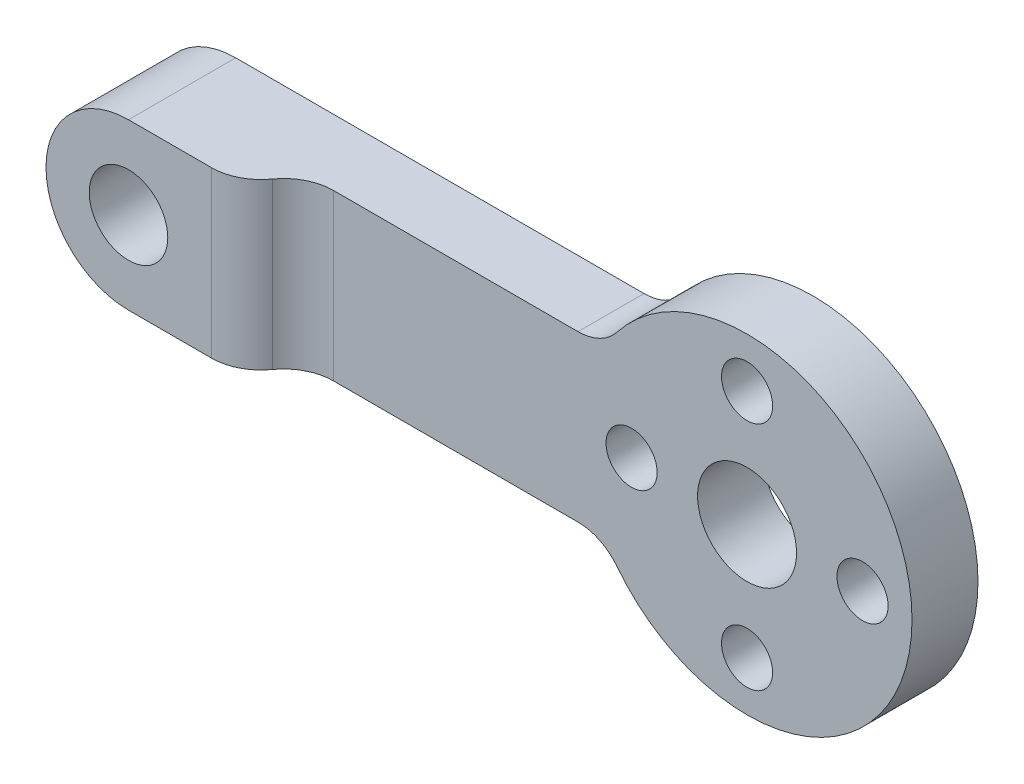
SolidWorks part; units mm, degrees
ref_plane "Front Plane" through (0, 0, 0) normal (0, 0, 1) x (1, 0, 0)
ref_plane "Top Plane" through (0, 0, 0) normal (0, 1, 0) x (1, 0, 0)
ref_plane "Right Plane" through (0, 0, 0) normal (1, 0, 0) x (0, 0, -1)
sketch "Sketch8" plane through (0, 0, 0) normal (0, 0, 1) x (1, 0, 0)
  line L0 (23.6603, 5) -> (25, 5) construction
  line L1 (-25, -5) -> (6.3397, -5)
  line L2 (-25, -5) -> (-25, 5)
  line L3 (-25, 5) -> (6.3397, 5)
  line L4 (25, -5) -> (25, 5) construction
  line L5 (23.6603, -5) -> (25, -5) construction
  line L6 (-25, 5) -> (25, -5) construction
  arc A0 (6.3397, -5) -> (6.3397, 5) centre (15, 0) ccw
  point P6 (25, 0)
  point P8 (0, 0)
  point P12 (0, 0)
  dimension "D1" = 20
  dimension "D2" = 50
  dimension "D3" = 10
extrude "Boss-Extrude3" add sketch "Sketch8" along normal blind 6.5
sketch "Sketch9" plane through (0, 0, 6.5) normal (0, 0, 1) x (1, 0, 0)
  line L0 (-25, 5) -> (-25, -5) construction
  line L2 (6.3397, 5) -> (-25, 5) construction
  circle A0 centre (-20, 0) radius 2.3813
  circle A1 centre (15, 0) radius 3
  circle A2 centre (22, 0) radius 1.55
  circle A3 centre (15, -7) radius 1.55
  circle A4 centre (8, 0) radius 1.55
  circle A5 centre (15, 7) radius 1.55
  point P7 (0, 0)
  point P16 (-25, 0)
  dimension "D1" = 4.7625
  dimension "D2" = 6
  dimension "D4" = 3.1
  dimension "D3" = 7
  dimension "D6" = 5
  dimension "D7" = 5
  dimension "D5" = 4
extrude "Cut-Extrude4" cut sketch "Sketch9" against normal up to surface (6.5 mm away) up to face at (-4.6651, 0, 0)
sketch "Sketch10" plane through (0, 0, 0) normal (0, 1, 0) x (1, 0, 0)
  line L1 (25, -6.5) -> (-12, -6.5)
  line L2 (25, -6.5) -> (25, -4)
  line L3 (25, -4) -> (-12, -4)
  line L4 (-12, -6.5) -> (-12, -4)
  line L8 (25, 0) -> (6.3397, 0) construction
  line L9 (-25, -6.5) -> (-25, 0) construction
  dimension "D1" = 13
  dimension "D3" = 4
extrude "Cut-Extrude5" cut sketch "Sketch10" against normal mid plane 30
fillet "Fillet6" radius 3 1 edges at (-12, 0, 6.5)
fillet "Fillet7" radius 3 3 edges at (-12, 0, 4) (6.3397, -5, 2) (6.3397, 5, 2)
fillet "Fillet8" 2 edges at (-25, 5, 3.25) (-25, -5, 3.25) type full round first side face at (-11.1511, 5, 3.75) second side face at (-11.1511, -5, 3.75) middle face at (-25, 0, 3.25)
equation "\"length\" = 50"
equation "\"pin_hole_diameter\"= 3in / 16"
equation "\"bolt_hold_diameter\"= 3.05mm"
equation "\"bearing_length\"= 5in / 16"
equation "\"D2@Sketch8\"=\"length\""
equation "\"D1@Sketch9\"=\"pin_hole_diameter\""
equation "\"D7@Sketch9\"=\"D6@Sketch9\""
